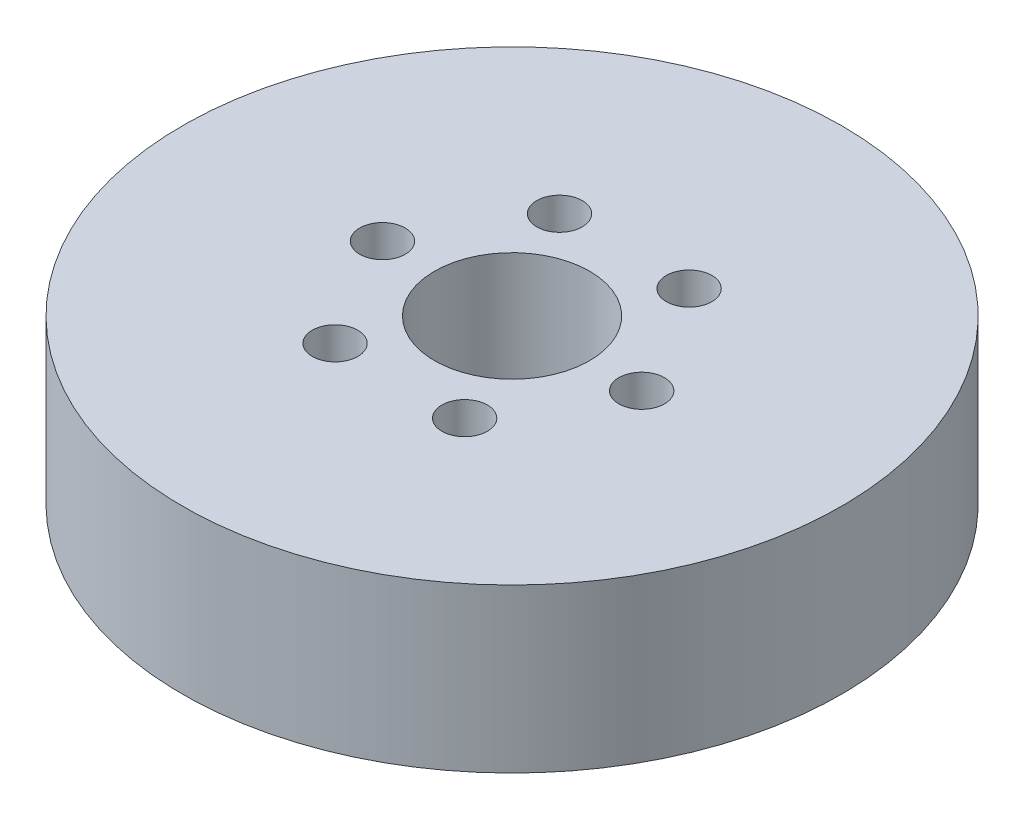
SolidWorks part; units mm, degrees
ref_plane "Front Plane" through (0, 0, 0) normal (0, 0, 1) x (1, 0, 0)
ref_plane "Top Plane" through (0, 0, 0) normal (0, 1, 0) x (1, 0, 0)
ref_plane "Right Plane" through (0, 0, 0) normal (1, 0, 0) x (0, 0, -1)
sketch "Sketch1" plane through (0, 0, 0) normal (0, 1, 0) x (1, 0, 0)
  circle A0 centre (0, 0) radius 42.5
  dimension "FLANGE_OD" = 85
extrude "Boss-Extrude1" add sketch "Sketch1" along normal blind 21
sketch "Sketch2" plane through (0, 0, 0) normal (0, 1, 0) x (1, 0, 0)
  circle A0 centre (0, 0) radius 10
  dimension "BORE_D" = 20
extrude "Cut-Extrude1" cut sketch "Sketch2" along normal through all
sketch "Sketch3" plane through (0, 21, 0) normal (0, 1, 0) x (1, 0, 0)
  circle A0 centre (0, 0) radius 16.7113 construction
  circle A1 centre (-16.7113, 0) radius 2.9368
  dimension "BOLT_D" = 5.8735
  dimension "BOLT_PCD" = 33.4225
extrude "Cut-Extrude2" cut sketch "Sketch3" against normal blind 19.6518
pattern_circular "CirPattern1" count 6 over 360 about axis through (0, 0, 0) along (0, 1, 0) of "Cut-Extrude2"
